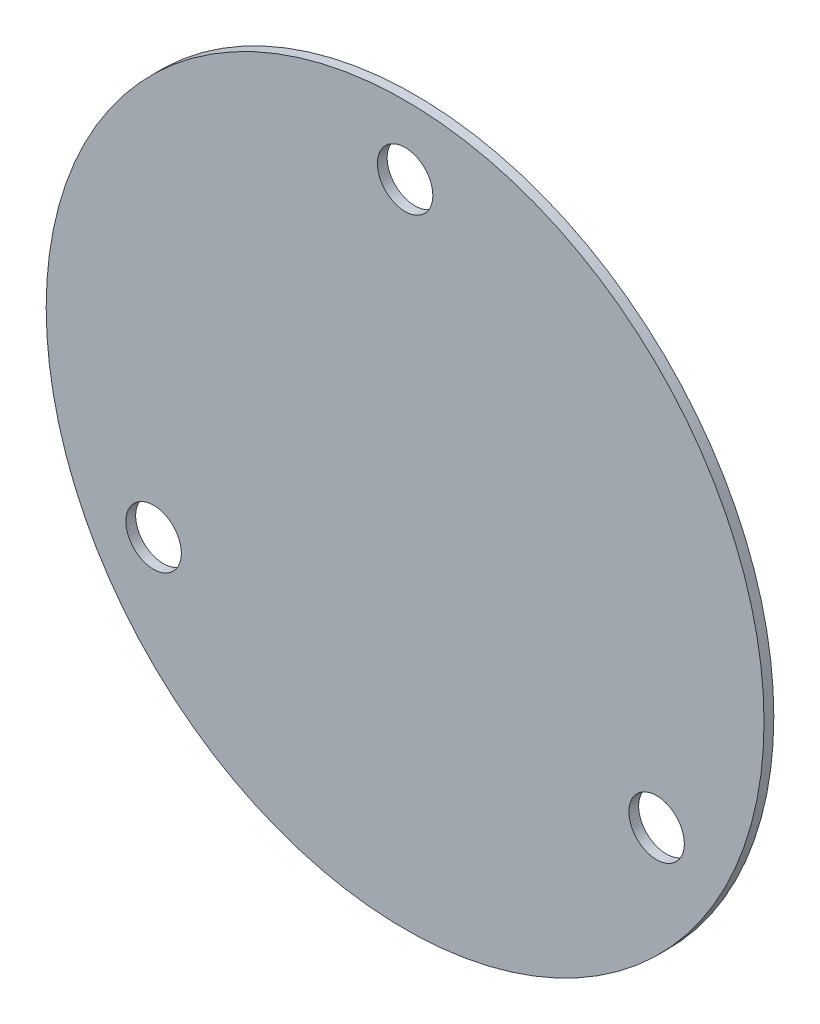
SolidWorks part; units mm, degrees
note: The reader was unsure of these and kept them because the rebuilt part matched: thickness of "Базовая кромка1", "Листовой металл5".
material "AISI 304"
ref_plane "Спереди" through (0, 0, 0) normal (0, 0, 1) x (1, 0, 0)
ref_plane "Сверху" through (0, 0, 0) normal (0, 1, 0) x (1, 0, 0)
ref_plane "Справа" through (0, 0, 0) normal (1, 0, 0) x (0, 0, -1)
sketch "Эскиз1" plane through (0, 0, 0) normal (0, 0, 1) x (1, 0, 0)
  line L0 (77.0763, 44.5) -> (0, 0) construction
  line L1 (0, 89) -> (0, 0) construction
  circle A0 centre (0, 0) radius 110
  circle A2 centre (0, 89) radius 8.5
  circle A3 centre (0, 0) radius 89 construction
  circle A4 centre (77.0763, 44.5) radius 8.5 construction
  circle A5 centre (77.0763, -44.5) radius 8.5
  circle A6 centre (0, -89) radius 8.5 construction
  circle A7 centre (-77.0763, -44.5) radius 8.5
  circle A8 centre (-77.0763, 44.5) radius 8.5 construction
  point P19 (0, 0)
  point P23 (0, 0)
  dimension "D1" = 220
  dimension "D3" = 17
  dimension "D4" = 178
  dimension "D6" = 60
  dimension "D5" = 6
base flange "Базовая кромка1" sketch "Эскиз1" thickness 3 reverse thickness direction no parameters "D1"=4
sketch "Сгиб-Линии1" plane through (0, 0, 0) normal (0, 1, 0) x (1, 0, 0)
sketch "Граничная рамка1" plane through (0, 0, 0) normal (0, 1, 0) x (1, 0, 0)
sheet metal parameters "Листовой металл5" thickness 3 parameters "D1"=4
flat pattern "Развертка5" [suppressed]
sketch "Сгиб-Линии2" plane through (0, 0, 0) normal (0, 1, 0) x (1, 0, 0)
sketch "Граничная рамка2" [suppressed] plane through (0, 0, 0) normal (0, 1, 0) x (1, 0, 0)
